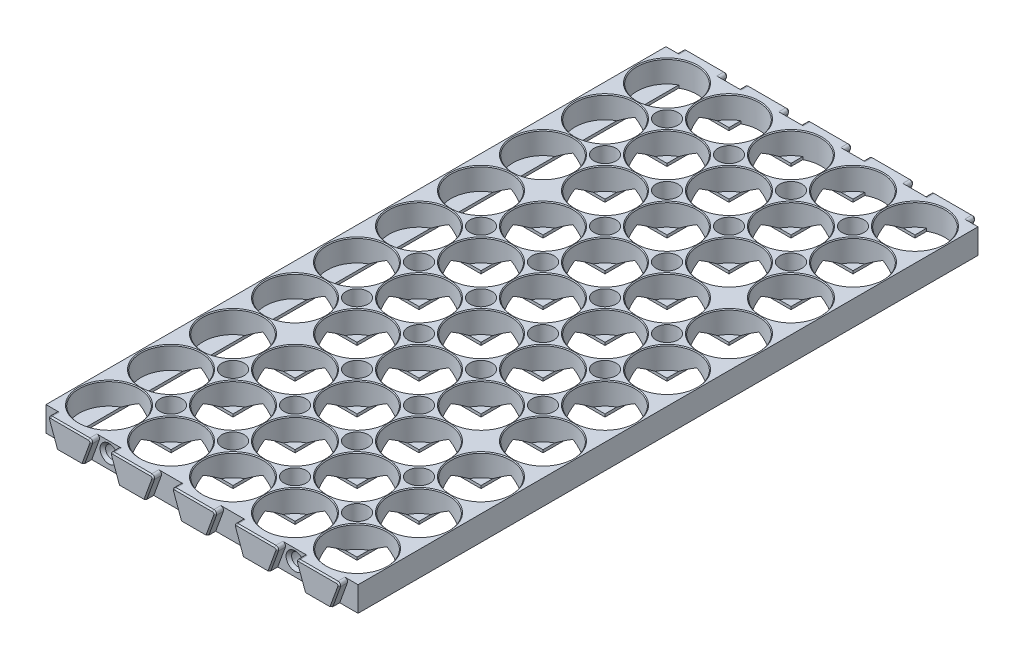
SolidWorks part; units mm, degrees
ref_plane "Front Plane" through (0, 0, 0) normal (0, 0, 1) x (1, 0, 0)
ref_plane "Top Plane" through (0, 0, 0) normal (0, 1, 0) x (1, 0, 0)
ref_plane "Right Plane" through (0, 0, 0) normal (1, 0, 0) x (0, 0, -1)
sketch "Sketch1" plane through (0, 0, 0) normal (0, 1, 0) x (1, 0, 0)
  line L0 (-11.25, 10.875) -> (11.25, 10.875) construction
  line L1 (-11.25, -11.25) -> (11.25, -11.25)
  line L2 (-11.25, -11.25) -> (-11.25, 11.25)
  line L3 (-11.25, 11.25) -> (11.25, 11.25)
  line L4 (11.25, -11.25) -> (11.25, 11.25)
  line L5 (-11.25, -11.25) -> (11.25, 11.25) construction
  line L6 (-11.25, 11.25) -> (11.25, -11.25) construction
  circle A0 centre (0, 0) radius 10.875
  point P0 (0, 0)
  dimension "D1" = 21.75
  dimension "D2" = 22.5
  dimension "D3" = 0.375
extrude "Boss-Extrude1" add sketch "Sketch1" along normal blind 8
sketch "Sketch2" plane through (0, 0, 0) normal (0, -1, 0) x (1, 0, 0)
  line L0 (5.25, 11.25) -> (-5.25, 11.25) construction
  line L1 (11.25, 11.25) -> (5.25, 11.25)
  line L2 (11.25, 11.25) -> (11.25, 5.25)
  line L3 (11.25, 5.25) -> (5.25, 5.25)
  line L4 (5.25, 11.25) -> (5.25, 5.25)
  line L5 (11.25, -11.25) -> (5.25, -11.25)
  line L6 (11.25, -11.25) -> (11.25, -5.25)
  line L7 (11.25, -5.25) -> (5.25, -5.25)
  line L8 (5.25, -11.25) -> (5.25, -5.25)
  line L9 (-11.25, -11.25) -> (-5.25, -11.25)
  line L10 (-11.25, -11.25) -> (-11.25, -5.25)
  line L11 (-11.25, -5.25) -> (-5.25, -5.25)
  line L12 (-5.25, -11.25) -> (-5.25, -5.25)
  line L13 (-11.25, 11.25) -> (-5.25, 11.25)
  line L14 (-11.25, 11.25) -> (-11.25, 5.25)
  line L15 (-11.25, 5.25) -> (-5.25, 5.25)
  line L16 (-5.25, 11.25) -> (-5.25, 5.25)
  line L17 (11.25, 5.25) -> (11.25, -5.25) construction
  line L18 (5.25, -11.25) -> (-5.25, -11.25) construction
  line L19 (-11.25, 5.25) -> (-11.25, -5.25) construction
  dimension "D1" = 10.5
extrude "Boss-Extrude2" add sketch "Sketch2" along normal blind 1
chamfer "Chamfer2" distance 0.3 angle 45 1 edges at (0, 8, 10.875)
pattern_linear "LPattern1" count 10 spacing 22.5 along (0, 0, 1) count 5 spacing 22.5 along (1, 0, 0) of "Boss-Extrude2", "Boss-Extrude1", "Chamfer2"
sketch "Sketch5" plane through (0, 0, -5.25) normal (0, 0, 1) x (1, 0, 0)
  line L25 (-5.25, -1) -> (-5.25, 0) construction
  line L26 (-5.25, -1) -> (-11.25, -1) construction
  line L27 (-11.25, -1) -> (-11.25, 0) construction
  line L29 (-5.25, 0) -> (-9.5238, 0) construction
  line L35 (-5.25, -1) -> (-5.25, 0)
  line L36 (-5.25, -1) -> (-11.25, -1)
  line L37 (-11.25, -1) -> (-11.25, 0)
  line L39 (-5.25, 0) -> (-11.25, 0)
  line L55 (101.25, -1) -> (95.25, -1)
  line L56 (101.25, -1) -> (101.25, 0)
  line L57 (101.25, 0) -> (95.25, 0)
  line L58 (95.25, -1) -> (95.25, 0)
  dimension "D1" = 6
extrude "Boss-Extrude3" add sketch "Sketch5" along normal up to surface (219 mm away)
sketch "Sketch6" plane through (0, 0, 0) normal (0, -1, 0) x (1, 0, 0)
  line L27 (39.75, -11.25) -> (50.25, -11.25) construction
  line L28 (50.25, -11.25) -> (50.25, -9.5238) construction
  line L29 (39.75, -9.5238) -> (39.75, -11.25) construction
  line L30 (17.25, -9.5238) -> (17.25, -11.25) construction
  line L31 (17.25, -11.25) -> (27.75, -11.25) construction
  line L32 (27.75, -11.25) -> (27.75, -9.5238) construction
  line L33 (-5.25, -9.5238) -> (-5.25, -11.25) construction
  line L34 (-5.25, -11.25) -> (5.25, -11.25) construction
  line L35 (5.25, -11.25) -> (5.25, -9.5238) construction
  line L51 (39.75, -11.25) -> (50.25, -11.25)
  line L52 (50.25, -11.25) -> (50.25, -9.5238)
  line L53 (39.75, -9.5238) -> (39.75, -11.25)
  line L54 (17.25, -9.5238) -> (17.25, -11.25)
  line L55 (17.25, -11.25) -> (27.75, -11.25)
  line L56 (27.75, -11.25) -> (27.75, -9.5238)
  line L57 (-5.25, -9.5238) -> (-5.25, -11.25)
  line L58 (-5.25, -11.25) -> (5.25, -11.25)
  line L59 (5.25, -11.25) -> (5.25, -9.5238)
  line L111 (50.25, 212.0238) -> (50.25, 213.75) construction
  line L112 (50.25, 213.75) -> (39.75, 213.75) construction
  line L113 (39.75, 213.75) -> (39.75, 212.0238) construction
  line L114 (27.75, 212.0238) -> (27.75, 213.75) construction
  line L115 (27.75, 213.75) -> (17.25, 213.75) construction
  line L116 (17.25, 213.75) -> (17.25, 212.0238) construction
  line L117 (5.25, 213.75) -> (-5.25, 213.75) construction
  line L118 (-5.25, 213.75) -> (-5.25, 212.0238) construction
  line L119 (5.25, 212.0238) -> (5.25, 213.75) construction
  line L123 (50.25, 212.0238) -> (50.25, 213.75)
  line L124 (50.25, 213.75) -> (39.75, 213.75)
  line L125 (39.75, 213.75) -> (39.75, 212.0238)
  line L126 (27.75, 212.0238) -> (27.75, 213.75)
  line L127 (27.75, 213.75) -> (17.25, 213.75)
  line L128 (17.25, 213.75) -> (17.25, 212.0238)
  line L129 (5.25, 213.75) -> (-5.25, 213.75)
  line L130 (-5.25, 213.75) -> (-5.25, 212.0238)
  line L131 (5.25, 212.0238) -> (5.25, 213.75)
  line L132 (95.25, 212.0238) -> (95.25, 213.75) construction
  line L133 (95.25, 213.75) -> (84.75, 213.75) construction
  line L134 (84.75, 213.75) -> (84.75, 212.0238) construction
  line L135 (84.75, -11.25) -> (95.25, -11.25)
  line L136 (95.25, -11.25) -> (95.25, -9.5238)
  line L137 (84.75, -9.5238) -> (84.75, -11.25)
  line L138 (84.75, -11.25) -> (95.25, -11.25)
  line L139 (95.25, -11.25) -> (95.25, -9.5238)
  line L140 (84.75, -9.5238) -> (84.75, -11.25)
  line L141 (62.25, -11.25) -> (72.75, -11.25)
  line L142 (72.75, -11.25) -> (72.75, -9.5238)
  line L143 (62.25, -9.5238) -> (62.25, -11.25)
  line L144 (62.25, -11.25) -> (72.75, -11.25)
  line L145 (72.75, -11.25) -> (72.75, -9.5238)
  line L146 (62.25, -9.5238) -> (62.25, -11.25)
  line L147 (72.75, 212.0238) -> (72.75, 213.75) construction
  line L148 (72.75, 213.75) -> (62.25, 213.75) construction
  line L149 (62.25, 213.75) -> (62.25, 212.0238) construction
  line L150 (95.25, 212.0238) -> (95.25, 213.75)
  line L151 (95.25, 213.75) -> (84.75, 213.75)
  line L152 (84.75, 213.75) -> (84.75, 212.0238)
  line L153 (72.75, 212.0238) -> (72.75, 213.75)
  line L154 (72.75, 213.75) -> (62.25, 213.75)
  line L155 (62.25, 213.75) -> (62.25, 212.0238)
  arc A9 (39.75, -9.5238) -> (50.25, -9.5238) centre (45, 0) ccw construction
  arc A10 (17.25, -9.5238) -> (27.75, -9.5238) centre (22.5, 0) ccw construction
  arc A11 (-5.25, -9.5238) -> (5.25, -9.5238) centre (0, 0) ccw construction
  arc A17 (39.75, -9.5238) -> (50.25, -9.5238) centre (45, 0) ccw
  arc A18 (17.25, -9.5238) -> (27.75, -9.5238) centre (22.5, 0) ccw
  arc A19 (-5.25, -9.5238) -> (5.25, -9.5238) centre (0, 0) ccw
  arc A37 (50.25, 212.0238) -> (39.75, 212.0238) centre (45, 202.5) ccw construction
  arc A38 (27.75, 212.0238) -> (17.25, 212.0238) centre (22.5, 202.5) ccw construction
  arc A39 (5.25, 212.0238) -> (-5.25, 212.0238) centre (0, 202.5) ccw construction
  arc A41 (50.25, 212.0238) -> (39.75, 212.0238) centre (45, 202.5) ccw
  arc A42 (27.75, 212.0238) -> (17.25, 212.0238) centre (22.5, 202.5) ccw
  arc A43 (5.25, 212.0238) -> (-5.25, 212.0238) centre (0, 202.5) ccw
  arc A45 (84.75, -9.5238) -> (95.25, -9.5238) centre (90, 0) ccw
  arc A46 (84.75, -9.5238) -> (95.25, -9.5238) centre (90, 0) ccw
  arc A47 (95.25, 212.0238) -> (84.75, 212.0238) centre (90, 202.5) ccw construction
  arc A48 (62.25, -9.5238) -> (72.75, -9.5238) centre (67.5, 0) ccw
  arc A49 (62.25, -9.5238) -> (72.75, -9.5238) centre (67.5, 0) ccw
  arc A50 (72.75, 212.0238) -> (62.25, 212.0238) centre (67.5, 202.5) ccw construction
  arc A51 (95.25, 212.0238) -> (84.75, 212.0238) centre (90, 202.5) ccw
  arc A52 (72.75, 212.0238) -> (62.25, 212.0238) centre (67.5, 202.5) ccw
  dimension "D1" = 0
  dimension "D2" = 0
extrude "Boss-Extrude4" add sketch "Sketch6" along normal up to surface (1 mm away) up to face at (-8.25, -1, 101.25)
sketch "Sketch7" plane through (0, 0, 0) normal (0, 0, 1) x (1, 0, 0)
  line L0 (84.75, 0) -> (90, 3.0311)
  line L1 (-5.25, 0) -> (5.25, 0)
  line L2 (-5.25, 0) -> (0, 5.25) construction
  line L3 (0, 5.25) -> (5.25, 0) construction
  line L4 (0, 0) -> (0, 8) construction
  line L5 (-11.25, 8) -> (101.25, 8) construction
  line L6 (-5.25, 0) -> (0, 3.0311)
  line L7 (0, 3.0311) -> (5.25, 0)
  line L8 (90, 3.0311) -> (95.25, 0)
  line L9 (-5.25, -1) -> (-5.25, 0) construction
  line L10 (5.25, -1) -> (5.25, 0) construction
  line L11 (-5.25, -1) -> (-5.25, 0) construction
  line L12 (5.25, -1) -> (5.25, 0) construction
  line L13 (17.25, 0) -> (22.5, 3.0311)
  line L14 (22.5, 3.0311) -> (27.75, 0)
  line L15 (17.25, 0) -> (27.75, 0)
  line L16 (39.75, 0) -> (45, 3.0311)
  line L17 (45, 3.0311) -> (50.25, 0)
  line L18 (39.75, 0) -> (50.25, 0)
  line L19 (62.25, 0) -> (67.5, 3.0311)
  line L20 (67.5, 3.0311) -> (72.75, 0)
  line L21 (62.25, 0) -> (72.75, 0)
  line L22 (-5.25, 0) -> (17.25, 0) construction
  line L23 (84.75, 0) -> (95.25, 0)
  dimension "D1" = 45
  dimension "D2" = 30
  dimension "D3" = 4.9689
  dimension "D5" = 22.5
  dimension "D4" = 5
extrude "Cut-Extrude1" cut sketch "Sketch7" along normal up to surface (207.75 mm away) up to face at (11.25, -0.3333, 207.75)
sketch "Sketch16" plane through (0, 0, 0) normal (1, 0, 0) x (0, 0, -1)
  line L2 (-5.25, -1) -> (-5.25, 0) construction
  line L3 (5.25, -1) -> (5.25, 0) construction
  line L4 (-5.25, 0) -> (0, 3.0311)
  line L5 (0, 3.0311) -> (5.25, 0)
  line L6 (-5.25, 0) -> (5.25, 0)
  line L7 (-5.25, -1) -> (-5.25, 0) construction
  line L8 (5.25, -1) -> (5.25, 0) construction
  line L9 (-22.5, 3.0311) -> (-17.25, 0)
  line L10 (-27.75, 0) -> (-17.25, 0)
  line L11 (-27.75, 0) -> (-22.5, 3.0311)
  line L12 (-45, 3.0311) -> (-39.75, 0)
  line L13 (-50.25, 0) -> (-39.75, 0)
  line L14 (-50.25, 0) -> (-45, 3.0311)
  line L15 (-67.5, 3.0311) -> (-62.25, 0)
  line L16 (-72.75, 0) -> (-62.25, 0)
  line L17 (-72.75, 0) -> (-67.5, 3.0311)
  line L18 (-90, 3.0311) -> (-84.75, 0)
  line L19 (-95.25, 0) -> (-84.75, 0)
  line L20 (-95.25, 0) -> (-90, 3.0311)
  line L21 (-112.5, 3.0311) -> (-107.25, 0)
  line L22 (-117.75, 0) -> (-107.25, 0)
  line L23 (-117.75, 0) -> (-112.5, 3.0311)
  line L24 (-135, 3.0311) -> (-129.75, 0)
  line L25 (-140.25, 0) -> (-129.75, 0)
  line L26 (-140.25, 0) -> (-135, 3.0311)
  line L27 (-157.5, 3.0311) -> (-152.25, 0)
  line L28 (-162.75, 0) -> (-152.25, 0)
  line L29 (-162.75, 0) -> (-157.5, 3.0311)
  line L30 (-180, 3.0311) -> (-174.75, 0)
  line L31 (-185.25, 0) -> (-174.75, 0)
  line L32 (-185.25, 0) -> (-180, 3.0311)
  line L33 (-202.5, 3.0311) -> (-197.25, 0)
  line L34 (-207.75, 0) -> (-197.25, 0)
  line L35 (-207.75, 0) -> (-202.5, 3.0311)
  line L42 (0, 3.0311) -> (-22.5, 3.0311) construction
  dimension "D1" = 30
  dimension "D3" = 22.5
  dimension "D2" = 10
extrude "Cut-Extrude7" cut sketch "Sketch16" along normal up to surface (84.75 mm away) up to face at (84.75, -0.3333, 11.25)
sketch "Sketch8" plane through (0, 0, -11.25) normal (0, 0, -1) x (-1, 0, 0)
  line L0 (0, -1) -> (0, 8) construction
  line L1 (-27.4743, -1) -> (-30.75, 8)
  line L2 (-101.25, 8) -> (11.25, 8) construction
  line L3 (4.9743, -1) -> (-4.9743, -1)
  line L4 (-4.9743, -1) -> (-8.25, 8)
  line L5 (-8.25, 8) -> (8.25, 8)
  line L6 (4.9743, -1) -> (8.25, 8)
  line L7 (11.25, 8) -> (11.25, -1) construction
  line L8 (11.25, -1) -> (-101.25, -1) construction
  line L9 (-30.75, 8) -> (-14.25, 8)
  line L10 (-101.25, 8) -> (11.25, 8) construction
  line L11 (-17.5257, -1) -> (-14.25, 8)
  line L12 (-17.5257, -1) -> (-27.4743, -1)
  line L13 (-49.9743, -1) -> (-53.25, 8)
  line L14 (-53.25, 8) -> (-36.75, 8)
  line L15 (-40.0257, -1) -> (-36.75, 8)
  line L16 (-40.0257, -1) -> (-49.9743, -1)
  line L17 (-72.4743, -1) -> (-75.75, 8)
  line L18 (-75.75, 8) -> (-59.25, 8)
  line L19 (-62.5257, -1) -> (-59.25, 8)
  line L20 (-62.5257, -1) -> (-72.4743, -1)
  line L21 (-4.9743, -1) -> (-27.4743, -1) construction
  line L22 (-101.25, 8) -> (11.25, 8) construction
  line L23 (-94.9743, -1) -> (-98.25, 8)
  line L24 (-98.25, 8) -> (-81.75, 8)
  line L25 (-85.0257, -1) -> (-81.75, 8)
  line L26 (-85.0257, -1) -> (-94.9743, -1)
  dimension "D1" = 70
  dimension "D2" = 3
  dimension "D4" = 22.5
  dimension "D5" = 9
sketch "Sketch9" plane through (0, 0, 213.75) normal (0, 0, 1) x (1, 0, 0)
  line L0 (85.0257, -1) -> (94.9743, -1) construction
  line L3 (94.9743, -1) -> (98.25, 8) construction
  line L20 (98.25, 8) -> (81.75, 8) construction
  line L21 (85.0257, -1) -> (81.75, 8) construction
  line L22 (85.0257, -1) -> (94.9743, -1)
  line L23 (94.9743, -1) -> (98.25, 8)
  line L24 (-4.9743, -1) -> (4.9743, -1)
  line L25 (4.9743, -1) -> (8.25, 8)
  line L26 (8.25, 8) -> (-8.25, 8)
  line L27 (-8.25, 8) -> (-4.9743, -1)
  line L28 (-4.9743, -1) -> (4.9743, -1)
  line L29 (4.9743, -1) -> (8.25, 8)
  line L30 (8.25, 8) -> (-8.25, 8)
  line L31 (-8.25, 8) -> (-4.9743, -1)
  line L32 (72.4743, -1) -> (75.75, 8)
  line L33 (75.75, 8) -> (59.25, 8)
  line L34 (59.25, 8) -> (62.5257, -1)
  line L35 (62.5257, -1) -> (72.4743, -1)
  line L36 (72.4743, -1) -> (75.75, 8)
  line L37 (75.75, 8) -> (59.25, 8)
  line L38 (59.25, 8) -> (62.5257, -1)
  line L39 (62.5257, -1) -> (72.4743, -1)
  line L40 (49.9743, -1) -> (53.25, 8)
  line L41 (53.25, 8) -> (36.75, 8)
  line L42 (36.75, 8) -> (40.0257, -1)
  line L43 (40.0257, -1) -> (49.9743, -1)
  line L44 (49.9743, -1) -> (53.25, 8)
  line L45 (53.25, 8) -> (36.75, 8)
  line L46 (36.75, 8) -> (40.0257, -1)
  line L47 (40.0257, -1) -> (49.9743, -1)
  line L48 (14.25, 8) -> (17.5257, -1)
  line L49 (17.5257, -1) -> (27.4743, -1)
  line L50 (27.4743, -1) -> (30.75, 8)
  line L51 (30.75, 8) -> (14.25, 8)
  line L52 (14.25, 8) -> (17.5257, -1)
  line L53 (17.5257, -1) -> (27.4743, -1)
  line L54 (27.4743, -1) -> (30.75, 8)
  line L55 (30.75, 8) -> (14.25, 8)
  line L56 (98.25, 8) -> (81.75, 8)
  line L57 (85.0257, -1) -> (81.75, 8)
  dimension "D1" = 0
  dimension "D2" = 0
  dimension "D3" = 0
  dimension "D4" = 0
extrude "Boss-Extrude5" add sketch "Sketch8" along normal blind 3
extrude "Boss-Extrude6" add sketch "Sketch9" along normal blind 3
fillet "Fillet1" radius 1 20 edges at (-8.25, 8, 215.25) (8.25, 8, 215.25) (14.25, 8, 215.25) (30.75, 8, 215.25) (36.75, 8, 215.25) (53.25, 8, 215.25) (59.25, 8, 215.25) (75.75, 8, 215.25) (81.75, 8, 215.25) (98.25, 8, 215.25) (98.25, 8, -12.75) (81.75, 8, -12.75) (75.75, 8, -12.75) (59.25, 8, -12.75) (53.25, 8, -12.75) (36.75, 8, -12.75) (30.75, 8, -12.75) (14.25, 8, -12.75) (8.25, 8, -12.75) (-8.25, 8, -12.75)
chamfer "Chamfer3" distance 0.5 angle 45 50 edges at (6.3679, 2.829, -14.25) (0, 8, -14.25) (-6.3679, 2.829, -14.25) (73.8679, 2.829, -14.25) (67.5, 8, -14.25) (61.1321, 2.829, -14.25) (51.3679, 2.829, -14.25) (45, 8, -14.25) (38.6321, 2.829, -14.25) (28.8679, 2.829, -14.25) (22.5, 8, -14.25) (16.1321, 2.829, -14.25) (73.8679, 2.829, 216.75) (61.1321, 2.829, 216.75) (67.5, 8, 216.75) (51.3679, 2.829, 216.75) (38.6321, 2.829, 216.75) (45, 8, 216.75) (28.8679, 2.829, 216.75) (16.1321, 2.829, 216.75) (22.5, 8, 216.75) (6.3679, 2.829, 216.75) (-6.3679, 2.829, 216.75) (0, 8, 216.75) (96.3679, 2.829, -14.25) (83.6321, 2.829, -14.25) (90, 8, -14.25) (96.3679, 2.829, 216.75) (90, 8, 216.75) (83.6321, 2.829, 216.75) (82.359, 7.5736, -14.25) (97.641, 7.5736, -14.25) (97.641, 7.5736, 216.75) (82.359, 7.5736, 216.75) (75.141, 7.5736, 216.75) (59.859, 7.5736, 216.75) (52.641, 7.5736, 216.75) (37.359, 7.5736, 216.75) (30.141, 7.5736, 216.75) (14.859, 7.5736, 216.75) (7.641, 7.5736, 216.75) (-7.641, 7.5736, 216.75) (75.141, 7.5736, -14.25) (59.859, 7.5736, -14.25) (52.641, 7.5736, -14.25) (37.359, 7.5736, -14.25) (30.141, 7.5736, -14.25) (14.859, 7.5736, -14.25) (7.641, 7.5736, -14.25) (-7.641, 7.5736, -14.25)
sketch "Sketch10" plane through (0, 0, -11.25) normal (0, 0, -1) x (-1, 0, 0)
  line L0 (-11.25, -1) -> (-11.25, 8) construction
  line L1 (-51.8219, 8) -> (-38.1781, 8) construction
  line L2 (-4.9743, -1) -> (-17.5257, -1) construction
  line L3 (-49.4422, -1) -> (-40.5578, -1) construction
  line L4 (-14.25, 8) -> (-8.25, 8) construction
  line L5 (-45, 8) -> (-45, -1) construction
  circle A0 centre (-11.25, 4) radius 2.25
  circle A1 centre (-78.75, 4) radius 2.25
  dimension "D2" = 4.5
  dimension "D1" = 4
sketch "Sketch11" plane through (0, 0, 213.75) normal (0, 0, 1) x (1, 0, 0)
  circle A0 centre (11.25, 4) radius 2.25 construction
  circle A1 centre (11.25, 4) radius 2.25
  circle A2 centre (78.75, 4) radius 2.25 construction
  circle A3 centre (78.75, 4) radius 2.25
extrude "Cut-Extrude2" cut sketch "Sketch10" against normal blind 5
extrude "Cut-Extrude3" cut sketch "Sketch11" against normal blind 5
chamfer "Chamfer5" distance 1 angle 45 4 edges at (81, 4, -11.25) (9, 4, -11.25) (13.5, 4, 213.75) (81, 4, 213.75)
sketch "Sketch17" plane through (0, -1, 0) normal (0, -1, 0) x (1, 0, 0)
  line L0 (5.25, 5.25) -> (17.25, 17.25) construction
  line L1 (11.25, 11.25) -> (33.75, 11.25) construction
  line L2 (5.25, 185.25) -> (17.25, 197.25) construction
  line L3 (84.75, 197.25) -> (72.75, 185.25) construction
  circle A0 centre (11.25, 11.25) radius 4
  circle A1 centre (33.75, 11.25) radius 4
  circle A2 centre (56.25, 11.25) radius 4
  circle A33 centre (33.75, 146.25) radius 4 [skipped]
  circle A34 centre (56.25, 146.25) radius 4 [skipped]
  circle A35 centre (33.75, 168.75) radius 4 [skipped]
  circle A36 centre (33.75, 191.25) radius 4 [skipped]
  circle A37 centre (56.25, 191.25) radius 4 [skipped]
  circle A38 centre (33.75, 213.75) radius 4 [skipped]
  circle A39 centre (56.25, 213.75) radius 4 [skipped]
  circle A40 centre (33.75, 236.25) radius 4 [skipped]
  circle A41 centre (56.25, 236.25) radius 4 [skipped]
  circle A42 centre (11.25, 146.25) radius 4 [skipped]
  circle A43 centre (11.25, 191.25) radius 4 [skipped]
  circle A44 centre (11.25, 213.75) radius 4 [skipped]
  circle A45 centre (11.25, 236.25) radius 4 [skipped]
  circle A46 centre (56.25, 168.75) radius 4 construction
  circle A47 centre (11.25, 168.75) radius 4 construction
  circle A48 centre (33.75, 123.75) radius 4 [skipped]
  circle A49 centre (56.25, 123.75) radius 4 [skipped]
  circle A50 centre (11.25, 123.75) radius 4 [skipped]
  circle A57 centre (33.75, 33.75) radius 4 [skipped]
  circle A58 centre (33.75, 56.25) radius 4 [skipped]
  circle A59 centre (56.25, 56.25) radius 4 [skipped]
  circle A60 centre (33.75, 78.75) radius 4 [skipped]
  circle A61 centre (56.25, 78.75) radius 4 [skipped]
  circle A62 centre (33.75, 101.25) radius 4 [skipped]
  circle A63 centre (56.25, 101.25) radius 4 [skipped]
  circle A64 centre (11.25, 56.25) radius 4 [skipped]
  circle A65 centre (11.25, 78.75) radius 4 [skipped]
  circle A66 centre (11.25, 101.25) radius 4 [skipped]
  circle A67 centre (56.25, 33.75) radius 4 construction
  circle A68 centre (11.25, 33.75) radius 4 construction
  circle A87 centre (11.25, 258.75) radius 4 [skipped]
  circle A88 centre (33.75, 258.75) radius 4 [skipped]
  circle A89 centre (56.25, 258.75) radius 4 [skipped]
  circle A90 centre (11.25, 281.25) radius 4 [skipped]
  circle A91 centre (33.75, 281.25) radius 4 [skipped]
  circle A92 centre (56.25, 281.25) radius 4 [skipped]
  circle A93 centre (11.25, 33.75) radius 4
  circle A94 centre (33.75, 33.75) radius 4
  circle A95 centre (56.25, 33.75) radius 4
  circle A96 centre (11.25, 56.25) radius 4 construction
  circle A97 centre (33.75, 56.25) radius 4
  circle A98 centre (56.25, 56.25) radius 4
  circle A99 centre (11.25, 78.75) radius 4
  circle A100 centre (33.75, 78.75) radius 4
  circle A101 centre (56.25, 78.75) radius 4
  circle A102 centre (11.25, 101.25) radius 4
  circle A103 centre (33.75, 101.25) radius 4
  circle A104 centre (56.25, 101.25) radius 4
  circle A105 centre (11.25, 123.75) radius 4
  circle A106 centre (33.75, 123.75) radius 4
  circle A107 centre (56.25, 123.75) radius 4
  circle A108 centre (11.25, 146.25) radius 4 construction
  circle A109 centre (33.75, 146.25) radius 4
  circle A110 centre (56.25, 146.25) radius 4
  circle A111 centre (11.25, 168.75) radius 4
  circle A112 centre (33.75, 168.75) radius 4
  circle A113 centre (56.25, 168.75) radius 4
  circle A114 centre (11.25, 191.25) radius 4
  circle A115 centre (33.75, 191.25) radius 4
  circle A116 centre (56.25, 191.25) radius 4
  circle A117 centre (78.75, 11.25) radius 4
  circle A118 centre (78.75, 33.75) radius 4
  circle A119 centre (78.75, 56.25) radius 4 construction
  circle A120 centre (78.75, 78.75) radius 4
  circle A121 centre (78.75, 101.25) radius 4
  circle A122 centre (78.75, 123.75) radius 4
  circle A123 centre (78.75, 146.25) radius 4 construction
  circle A124 centre (78.75, 168.75) radius 4
  circle A125 centre (78.75, 191.25) radius 4
  circle A130 centre (78.75, 213.75) radius 4 [skipped]
  circle A131 centre (78.75, 236.25) radius 4 [skipped]
  circle A132 centre (78.75, 258.75) radius 4 [skipped]
  circle A133 centre (78.75, 281.25) radius 4 [skipped]
  dimension "D4" = 22.5
  dimension "D5" = 9
  dimension "D1" = 8
  dimension "D2" = 4
  dimension "D3" = 13
extrude "Cut-Extrude8" cut sketch "Sketch17" against normal through all
sketch "Sketch18" plane through (0, -1, 0) normal (0, -1, 0) x (1, 0, 0)
  line L0 (84.75, 50.25) -> (84.75, 62.25) construction
  line L2 (5.25, 140.25) -> (17.25, 152.25) construction
  line L3 (5.25, 50.25) -> (17.25, 62.25) construction
  line L4 (72.75, 50.25) -> (84.75, 62.25) construction
  line L5 (50.25, 50.25) -> (62.25, 50.25) construction
  line L7 (101.25, -11.25) -> (101.25, 213.75) construction
  line L38 (101.25, 101.25) -> (-11.25, 101.25) construction
  line L40 (-11.25, 213.75) -> (-11.25, -11.25) construction
  line L42 (72.75, 140.25) -> (84.75, 152.25) construction
  circle A0 centre (11.25, 56.25) radius 2.1
  circle A4 centre (78.75, 56.25) radius 2.1
  circle A7 centre (78.75, 146.25) radius 2.1
  circle A8 centre (11.25, 146.25) radius 2.1
  dimension "D1" = 4.2
extrude "Cut-Extrude9" cut sketch "Sketch18" against normal blind 4
sketch "Sketch19" plane through (0, -1, 0) normal (0, -1, 0) x (1, 0, 0)
  line L0 (101.25, 101.25) -> (-11.25, 101.25) construction
  line L2 (-11.25, 213.75) -> (-11.25, -11.25) construction
  line L3 (101.25, -11.25) -> (101.25, 213.75) construction
  circle A2 centre (78.75, 146.25) radius 1.7
  circle A3 centre (11.25, 56.25) radius 1.7
  circle A4 centre (11.25, 146.25) radius 1.7
  circle A5 centre (78.75, 56.25) radius 1.7
  dimension "D1" = 3.4
extrude "Cut-Extrude10" cut sketch "Sketch19" against normal offset from surface (7 mm away) 2 up to face at (33.75, 8, 74.75)
chamfer "Chamfer6" distance 1 angle 45 4 edges at (11.25, -1, 144.15) (11.25, -1, 54.15) (78.75, -1, 144.15) (78.75, -1, 54.15)
sketch "Sketch22" plane through (0, 8, 0) normal (0, 1, 0) x (1, 0, 0)
  line L0 (51.8219, -216.75) -> (38.1781, -216.75) construction
  line L1 (-11.25, 11.25) -> (-11.625, 11.25)
  line L2 (-11.25, 11.25) -> (-11.25, -213.75)
  line L3 (-11.25, -213.75) -> (-11.625, -213.75)
  line L4 (-11.625, 11.25) -> (-11.625, -213.75)
  line L5 (45, 14.25) -> (45, -216.75) construction
  line L7 (38.1781, 14.25) -> (51.8219, 14.25) construction
  line L13 (-11.25, -213.75) -> (-6.8219, -213.75) construction
  line L14 (101.625, 11.25) -> (101.625, -213.75)
  line L15 (101.25, -213.75) -> (101.625, -213.75)
  line L16 (101.25, 11.25) -> (101.25, -213.75)
  line L17 (101.25, 11.25) -> (101.625, 11.25)
  arc A1 (-5.25, 9.5238) -> (-5.25, -9.5238) centre (0, 0) ccw construction
  point P10 (-10.875, 0)
  dimension "D1" = 0.75
  dimension "D2" = 0.375
extrude "Boss-Extrude7" add sketch "Sketch22" against normal up to surface (9 mm away) up to face at (45, -1, 101.25)
sketch "Sketch14" plane through (0, -1, 0) normal (0, -1, 0) x (1, 0, 0)
  line L0 (-5.25, 11.25) -> (-11.625, 11.25) construction
  line L2 (-5.25, 101.25) -> (45, 101.25) construction
  line L19 (-5.25, 191.25) -> (-11.625, 191.25) construction
  line L30 (-5.25, 101.25) -> (-11.625, 101.25) construction
  line L39 (-6.25, 10.25) -> (-6.25, 12.25)
  line L40 (-10.25, 8.7941) -> (-10.25, 13.7059)
  line L51 (-10.25, 188.7941) -> (-6.25, 190.25)
  line L52 (-10.25, 103.7059) -> (-6.25, 102.25)
  line L53 (-6.25, 100.25) -> (-6.25, 102.25)
  line L56 (45, -14.25) -> (45, 216.75) construction
  line L57 (49.4422, -14.25) -> (40.5578, -14.25) construction
  line L58 (-5.25, -9.5238) -> (-5.25, 212.0238) construction
  line L59 (40.5578, 216.75) -> (49.4422, 216.75) construction
  line L66 (-10.25, 98.7941) -> (-10.25, 103.7059)
  line L67 (-10.25, 193.7059) -> (-6.25, 192.25)
  line L68 (-10.25, 193.7059) -> (-10.25, 188.7941)
  line L69 (-5.25, 9.5238) -> (-5.25, 12.9762) construction
  line L70 (-11.625, -11.25) -> (-11.625, 213.75) construction
  line L71 (-6.25, 192.25) -> (-6.25, 190.25)
  line L75 (-10.25, 8.7941) -> (-6.25, 10.25)
  line L76 (95.25, 101.25) -> (101.625, 101.25) construction
  line L77 (95.25, 191.25) -> (101.625, 191.25) construction
  line L78 (95.25, 11.25) -> (101.625, 11.25) construction
  line L79 (100.25, 13.7059) -> (96.25, 12.25)
  line L84 (100.25, 98.7941) -> (96.25, 100.25)
  line L93 (100.25, 8.7941) -> (96.25, 10.25)
  line L94 (96.25, 192.25) -> (96.25, 190.25)
  line L95 (100.25, 193.7059) -> (100.25, 188.7941)
  line L98 (-10.25, 98.7941) -> (-6.25, 100.25)
  line L109 (-10.25, 13.7059) -> (-6.25, 12.25)
  line L110 (100.25, 193.7059) -> (96.25, 192.25)
  line L111 (100.25, 98.7941) -> (100.25, 103.7059)
  line L112 (96.25, 100.25) -> (96.25, 102.25)
  line L113 (100.25, 103.7059) -> (96.25, 102.25)
  line L114 (100.25, 188.7941) -> (96.25, 190.25)
  line L115 (100.25, 8.7941) -> (100.25, 13.7059)
  line L116 (96.25, 10.25) -> (96.25, 12.25)
  point P7 (-6.25, 101.25)
  point P31 (-10.25, 101.25)
  point P51 (100.25, 101.25)
  point P52 (96.25, 101.25)
  dimension "D1" = 1
  dimension "D2" = 70
  dimension "D3" = 4
  dimension "D4" = 1.375
  dimension "D5" = 1
  dimension "D7" = 70
  dimension "D8" = 4
extrude "Cut-Extrude11" cut sketch "Sketch14" against normal blind 2
chamfer "Chamfer7" distance 0.5 angle 45 24 edges at (98.25, -1, 189.5221) (100.25, -1, 191.25) (96.25, -1, 191.25) (98.25, -1, 192.9779) (-8.25, -1, 189.5221) (-6.25, -1, 191.25) (-10.25, -1, 191.25) (-8.25, -1, 192.9779) (-6.25, -1, 101.25) (-8.25, -1, 99.5221) (-10.25, -1, 101.25) (-8.25, -1, 102.9779) (96.25, -1, 101.25) (98.25, -1, 99.5221) (100.25, -1, 101.25) (98.25, -1, 102.9779) (96.25, -1, 11.25) (98.25, -1, 9.5221) (100.25, -1, 11.25) (98.25, -1, 12.9779) (-6.25, -1, 11.25) (-8.25, -1, 12.9779) (-10.25, -1, 11.25) (-8.25, -1, 9.5221)
equation "\"cell_side\"= 22.50"
equation "\"D2@Sketch1\"=\"cell_side\""
equation "\"D5@Sketch7\"=\"cell_side\""
equation "\"D3@Sketch16\"=\"cell_side\""
equation "\"D4@Sketch8\"=\"cell_side\""
equation "\"D3@LPattern1\"=\"cell_side\""
equation "\"D4@LPattern1\"=\"cell_side\""
equation "\"D4@Sketch17\"=\"cell_side\""
